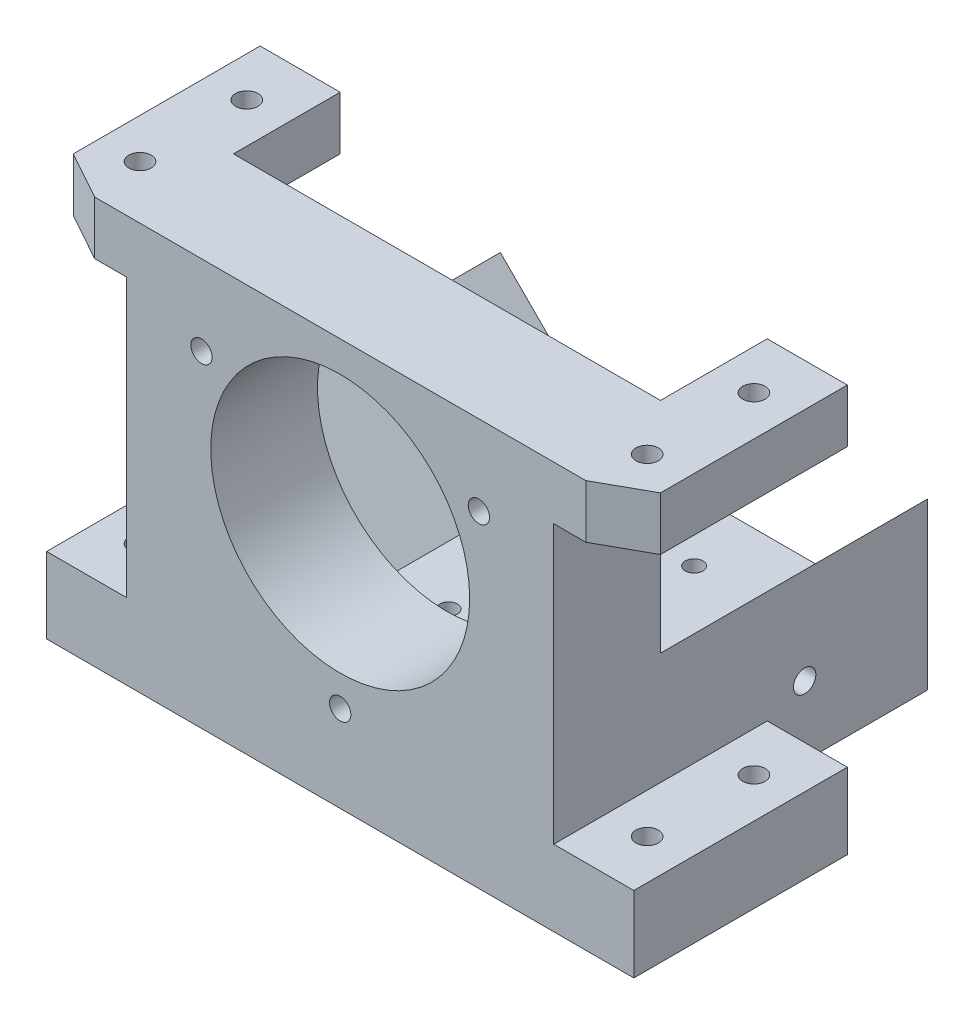
SolidWorks part; units mm, degrees
ref_plane "Front Plane" through (0, 0, 0) normal (0, 0, 1) x (1, 0, 0)
ref_plane "Top Plane" through (0, 0, 0) normal (0, 1, 0) x (1, 0, 0)
ref_plane "Right Plane" through (0, 0, 0) normal (1, 0, 0) x (0, 0, -1)
sketch "Sketch1" plane through (0, 0, 0) normal (0, 0, 1) x (1, 0, 0)
  line L1 (-40, -30) -> (40, -30)
  line L2 (-40, -30) -> (-40, 30)
  line L3 (-40, 30) -> (40, 30)
  line L4 (40, -30) -> (40, 30)
  line L5 (-40, -30) -> (40, 30) construction
  line L6 (-40, 30) -> (40, -30) construction
  circle A0 centre (0, 0) radius 24.25
  dimension "D1" = 48.5
  dimension "D2" = 80
  dimension "D3" = 60
extrude "Boss-Extrude1" add sketch "Sketch1" along normal blind 20
sketch "Sketch4" plane through (40, 0, 0) normal (1, 0, 0) x (0, 0, -1)
  line L0 (0, -30) -> (0, 30) construction
  line L1 (-20, 30) -> (0, 30)
  line L2 (-20, 30) -> (-20, 20)
  line L3 (-20, 20) -> (0, 20)
  line L5 (-20, 30) -> (0, 20) construction
  line L6 (-20, 20) -> (0, 30) construction
  line L8 (0, 30) -> (20, 30)
  line L10 (0, 20) -> (20, 20)
  line L11 (20, 30) -> (20, 20)
  line L12 (0, 30) -> (20, 20) construction
  line L13 (0, 20) -> (20, 30) construction
  point P4 (-10, 25)
  point P10 (10, 25)
  dimension "D1" = 10
extrude "Boss-Extrude3" add sketch "Sketch4" along normal blind 15
sketch "Sketch5" plane through (0, 30, 0) normal (0, 1, 0) x (1, 0, 0)
  line L0 (-40, -10) -> (55, -10) construction
  line L1 (55, 20) -> (55, -20) construction
  line L2 (46, -20) -> (55, -15)
  line L3 (40, 0) -> (40, -20) construction
  line L4 (40, 0) -> (-40, 0) construction
  line L5 (55, -20) -> (-40, -20) construction
  line L6 (-40, -20) -> (-40, 0) construction
  line L7 (55, 20) -> (55, -20) construction
  line L8 (40, 0) -> (55, 0) construction
  line L9 (55, -15) -> (55, -20)
  line L10 (55, -20) -> (46, -20)
  circle A0 centre (47.5, -10) radius 2.1
  circle A1 centre (47.5, 10) radius 2.1
  dimension "D1" = 4.2
  dimension "D2" = 7.5
  dimension "D3" = 9
  dimension "D4" = 5
extrude "Cut-Extrude2" cut sketch "Sketch5" against normal up to surface (10 mm away) up to face at (46, 20, 0)
sketch "Sketch6" plane through (0, -30, 0) normal (0, -1, 0) x (-1, 0, 0)
  line L1 (40, -20) -> (-40, -20)
  line L2 (40, -20) -> (40, 0)
  line L3 (40, 0) -> (-40, 0)
  line L4 (-40, -20) -> (-40, 0)
  line L5 (40, -20) -> (-40, 0) construction
  line L6 (40, 0) -> (-40, -20) construction
  point P4 (0, -10)
extrude "Boss-Extrude4" add sketch "Sketch6" along normal blind 2
sketch "Sketch8" plane through (0, 0, 0) normal (0, 0, -1) x (-1, 0, 0)
  line L0 (-40, -11) -> (-19, -32)
  line L1 (-40, -32) -> (-40, 20) construction
  line L2 (40, -32) -> (-40, -32) construction
  line L3 (-19, -32) -> (-40, -32)
  line L4 (-40, -32) -> (-40, -11)
  dimension "D1" = 21
extrude "Boss-Extrude6" add sketch "Sketch8" along normal blind 50
sketch "Sketch9" plane through (40, 0, 0) normal (1, 0, 0) x (0, 0, -1)
  line L0 (-20, -32) -> (-20, 20) construction
  line L1 (50, -32) -> (-20, -32) construction
  circle A0 centre (27, -29) radius 2.1
  dimension "D1" = 4.2
  dimension "D2" = 47
  dimension "D3" = 3
extrude "Cut-Extrude3" cut sketch "Sketch9" against normal through all
ref_plane "Plane1" through (19, 0, 0) normal (-1, 0, 0) x (0, 0, 1)
sketch "Sketch12" plane through (0, -32, 0) normal (0, -1, 0) x (1, 0, 0)
  line L0 (0, 20) -> (0, -50) construction
  line L1 (-40, 20) -> (40, 20)
  line L2 (-40, 20) -> (-40, -50)
  line L3 (-40, -50) -> (40, -50)
  line L4 (40, 20) -> (40, -50)
  line L5 (-40, 20) -> (40, -50) construction
  line L6 (-40, -50) -> (40, 20) construction
  line L7 (-8, -8.3) -> (8, -8.3) construction
  line L8 (-8, -8.3) -> (-8, -38.3) construction
  line L9 (-8, -38.3) -> (8, -38.3) construction
  line L10 (8, -38.3) -> (8, -8.3) construction
  line L11 (-40, 0) -> (19, 0) construction
  circle A0 centre (-8, -8.3) radius 1.65
  circle A1 centre (8, -8.3) radius 1.65
  circle A2 centre (8, -38.3) radius 1.65
  circle A3 centre (-8, -38.3) radius 1.65
  point P4 (0, -15)
  point P11 (0, -8.3)
  dimension "D4" = 3.3
  dimension "D1" = 16
  dimension "D2" = 30
  dimension "D3" = 8.3
extrude "Boss-Extrude8" add sketch "Sketch12" along normal blind 10
ref_plane "Plane2" through (0, 0, 0) normal (1, 0, 0) x (0, 0, -1)
mirror "Mirror1" about plane through (0, 0, 0) normal (1, 0, 0) of "Cut-Extrude3", "Boss-Extrude6", "Boss-Extrude4", "Cut-Extrude2", "Boss-Extrude3"
sketch "Sketch13" plane through (-40, 0, 0) normal (-1, 0, 0) x (0, 0, 1)
  line L0 (20, 20) -> (20, -42) construction
  line L1 (20, -42) -> (0, -42)
  line L2 (20, -42) -> (20, -32)
  line L3 (20, -32) -> (0, -32)
  line L5 (20, -42) -> (0, -32) construction
  line L6 (20, -32) -> (0, -42) construction
  line L7 (15, 20) -> (-20, 20) construction
  line L13 (-20, -42) -> (0, -42)
  line L14 (-20, -42) -> (-20, -32)
  line L15 (-20, -32) -> (0, -32)
  line L17 (-20, -42) -> (0, -32) construction
  line L18 (-20, -32) -> (0, -42) construction
  point P4 (10, -37)
  point P15 (-10, -37)
  dimension "D1" = 10
  dimension "D2" = 52
  dimension "D3" = 20
extrude "Boss-Extrude9" add sketch "Sketch13" along normal blind 15
sketch "Sketch14" plane through (0, -42, 0) normal (0, -1, 0) x (1, 0, 0)
  line L0 (-55, 0) -> (-27.8806, 0) construction
  line L1 (-55, -20) -> (-55, 20) construction
  circle A0 centre (-47.5, 10) radius 2.1
  circle A1 centre (-47.5, 10) radius 2.1 construction
  circle A2 centre (-47.5, -10) radius 2.1
extrude "Cut-Extrude4" cut sketch "Sketch14" against normal blind 10
mirror "Mirror2" about plane through (0, 0, 0) normal (1, 0, 0) of "Cut-Extrude4", "Boss-Extrude9"
sketch "Sketch15" plane through (0, -42, 0) normal (0, -1, 0) x (1, 0, 0)
  line L0 (-8, -8.3) -> (8, -8.3) construction
  line L1 (-55, 20) -> (55, 20)
  line L2 (-55, 20) -> (-55, -20)
  line L3 (-55, -20) -> (55, -20)
  line L4 (55, 20) -> (55, -20)
  line L5 (-55, 20) -> (55, -20) construction
  line L6 (-55, -20) -> (55, 20) construction
  line L7 (-8, -3.3) -> (8, -3.3)
  line L8 (-8, -13.3) -> (8, -13.3)
  circle A0 centre (-47.5, 10) radius 2.1
  circle A1 centre (-47.5, -10) radius 2.0834
  circle A2 centre (47.5, -10) radius 2
  circle A3 centre (47.5, 10) radius 2
  circle A4 centre (-47.5, 10) radius 2.1 construction
  arc A24 (-8, -3.3) -> (-8, -13.3) centre (-8, -8.3) ccw
  arc A25 (8, -13.3) -> (8, -3.3) centre (8, -8.3) ccw
  circle A26 centre (8, -8.3) radius 1.65 construction
  point P4 (0, 0)
  point P19 (0, -8.3)
  point P24 (13, -8.3)
  dimension "D1" = 5
extrude "Boss-Extrude10" add sketch "Sketch15" along normal blind 4.2
sketch "Sketch16" plane through (0, 0, 20) normal (0, 0, 1) x (1, 0, 0)
  line L0 (0, -34.1) -> (0, 34.1) construction
  line L1 (0, -30) -> (0, -24.25) construction
  line L2 (0, 0) -> (0, -30) construction
  circle A0 centre (0, -30) radius 2
  circle A1 centre (0, 0) radius 24.25 construction
  dimension "D1" = 4
  dimension "D2" = 30
extrude "Cut-Extrude5" cut sketch "Sketch16" against normal blind 3
pattern_circular "CirPattern1" count 3 every 120 about axis through (0, 0, 20) along (0, 0, 1) of "Cut-Extrude5"
